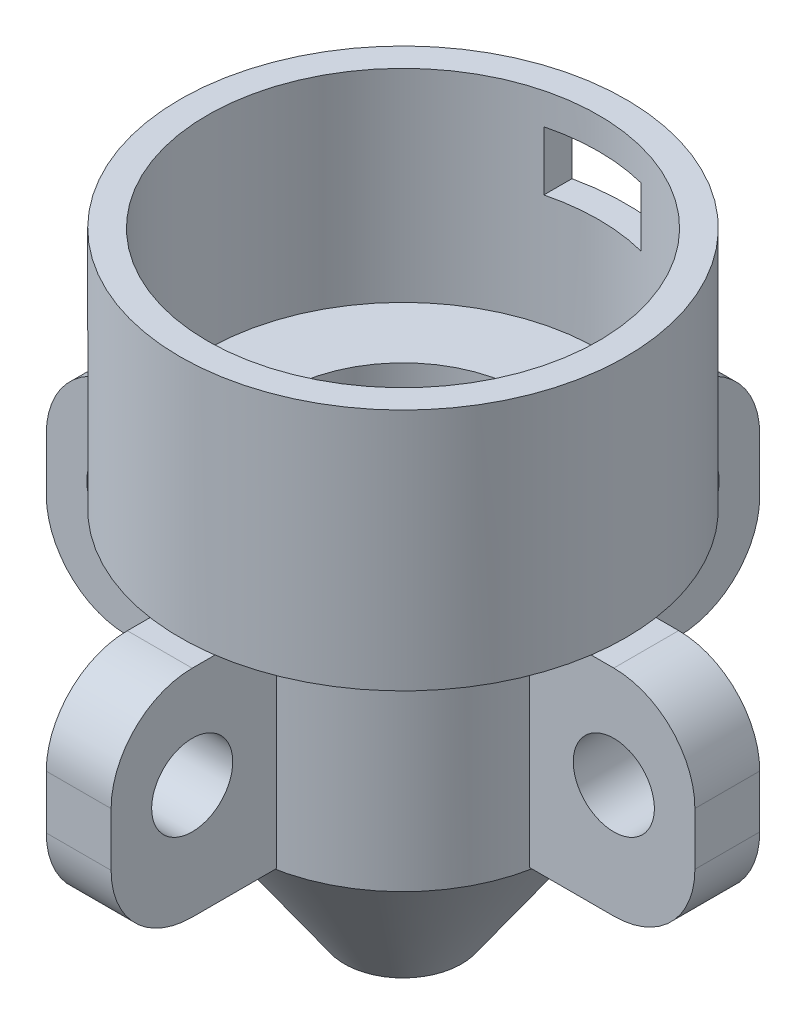
SolidWorks part; units mm, degrees
ref_plane "前视基准面" through (0, 0, 0) normal (0, 0, 1) x (1, 0, 0)
ref_plane "上视基准面" through (0, 0, 0) normal (0, 1, 0) x (1, 0, 0)
ref_plane "右视基准面" through (0, 0, 0) normal (1, 0, 0) x (0, 0, -1)
sketch "草图1" plane through (0, 0, 0) normal (0, 1, 0) x (1, 0, 0)
  circle A0 centre (0, 0) radius 55
extrude "凸台-拉伸1" add sketch "草图1" along normal blind 150
sketch "草图2" plane through (0, 0, 0) normal (0, -1, 0) x (1, 0, 0)
  circle A0 centre (0, 0) radius 30
extrude "切除-拉伸1" cut sketch "草图2" against normal blind 100
sketch "草图3" plane through (0, 150, 0) normal (0, 1, 0) x (1, 0, 0)
  circle A0 centre (0, 0) radius 48.25
extrude "切除-拉伸2" cut sketch "草图3" against normal blind 50
sketch "草图4" plane through (0, 0, 0) normal (0, -1, 0) x (1, 0, 0)
  circle A0 centre (0, 0) radius 40
extrude "切除-拉伸-薄壁1" cut sketch "草图4" against normal blind 90 thin thin type one direction wall 20
sketch "草图6" plane through (0, 0, 0) normal (0, 0, 1) x (1, 0, 0)
  line L1 (-8, 89.9737) -> (8, 89.9737)
  line L2 (-8, 89.9737) -> (-8, 36.7789)
  line L3 (-8, 36.7789) -> (8, 36.7789)
  line L4 (8, 89.9737) -> (8, 36.7789)
  line L5 (-8, 89.9737) -> (8, 36.7789) construction
  line L6 (-8, 36.7789) -> (8, 89.9737) construction
  point P0 (0, 63.3763)
extrude "凸台-拉伸3" add sketch "草图6" along normal blind 50 from offset 30 separate body
sketch "草图10" plane through (0, 0, 0) normal (0, 0, 1) x (1, 0, 0)
  line L0 (-8, 36.7789) -> (8, 36.7789)
  line L1 (8, 36.7789) -> (8, 89.9737)
  line L2 (8, 89.9737) -> (-8, 89.9737)
  line L3 (-8, 89.9737) -> (-8, 36.7789)
extrude "凸台-拉伸4" add sketch "草图10" against normal blind 50 from offset 30 separate body offset against normal yes
sketch "草图11" plane through (0, 0, 0) normal (1, 0, 0) x (0, 0, -1)
  line L0 (-40, 90) -> (40, 90) construction
  line L1 (8, 37) -> (-8, 37)
  line L2 (8, 37) -> (8, 90)
  line L3 (8, 90) -> (-8, 90)
  line L4 (-8, 37) -> (-8, 90)
  line L5 (8, 37) -> (-8, 90) construction
  line L6 (8, 90) -> (-8, 37) construction
  point P0 (0, 63.5)
extrude "凸台-拉伸6" add sketch "草图11" along normal blind 50 from offset 30
sketch "草图12" plane through (0, 0, 0) normal (1, 0, 0) x (0, 0, -1)
  line L0 (-8, 90) -> (-8, 37)
  line L1 (-8, 37) -> (8, 37)
  line L2 (8, 37) -> (8, 90)
  line L3 (8, 90) -> (-8, 90)
extrude "凸台-拉伸7" add sketch "草图12" against normal blind 50 from offset 30 offset against normal yes
fillet "圆角1" radius 20 2 edges at (-80, 90, 0) (-80, 37, 0)
fillet "圆角2" radius 20 2 edges at (0, 89.9737, -80) (0, 36.7789, -80)
fillet "圆角3" radius 20 2 edges at (80, 90, 0) (80, 37, 0)
fillet "圆角4" radius 20 2 edges at (0, 36.7789, 80) (0, 89.9737, 80)
sketch "草图15" plane through (0, 0, 0) normal (0, 0, 1) x (1, 0, 0)
  circle A0 centre (60, 65) radius 10
  circle A1 centre (-60, 65) radius 10
extrude "切除-拉伸4" cut sketch "草图15" against normal blind 40 and the other way blind 40
sketch "草图16" plane through (0, 0, 0) normal (1, 0, 0) x (0, 0, -1)
  circle A0 centre (60, 65) radius 10
  circle A1 centre (-60, 65) radius 10
extrude "切除-拉伸5" cut sketch "草图16" against normal blind 40 and the other way blind 40
sketch "草图17" plane through (0, 0, 0) normal (0, 0, 1) x (1, 0, 0)
  line L1 (-12, 127.7) -> (12, 127.7)
  line L2 (-12, 127.7) -> (-12, 142.2717)
  line L3 (-12, 142.2717) -> (12, 142.2717)
  line L4 (12, 127.7) -> (12, 142.2717)
  line L5 (-39.1918, 90) -> (39.1918, 90) construction
  dimension "D1" = 37.7
extrude "切除-拉伸6" cut sketch "草图17" against normal blind 87
sketch "草图18" plane through (0, 0, 0) normal (0, -1, 0) x (1, 0, 0)
  circle A0 centre (0, 0) radius 14
extrude "拉伸-薄壁1" add sketch "草图18" against normal blind 47 thin thin type one direction wall 20
chamfer "倒角1" distance 36.5 angle 35 1 edges at (0, 0, -40) first distance on face at (0, 0, -40)
